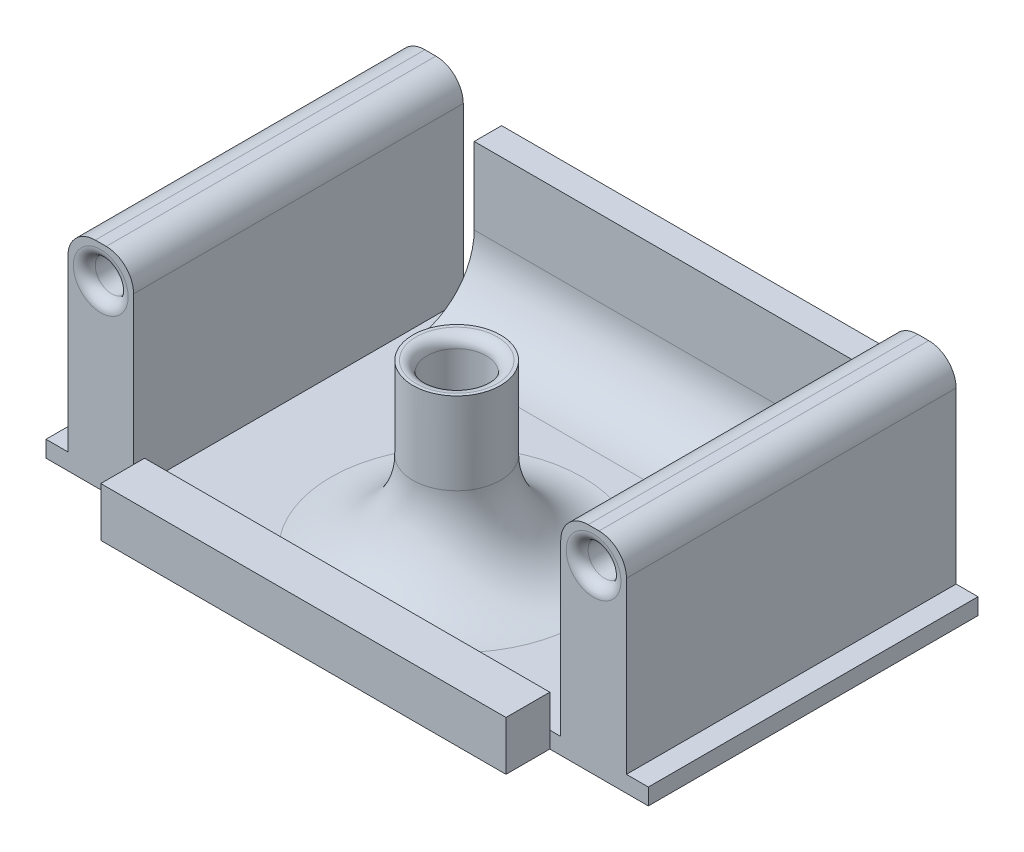
SolidWorks part; units mm, degrees
note: The reader was unsure of these and kept them because the rebuilt part matched: shared geometry of "Эскиз8<3>".
ref_plane "Спереди" through (0, 0, 0) normal (0, 0, 1) x (1, 0, 0)
ref_plane "Сверху" through (0, 0, 0) normal (0, 1, 0) x (1, 0, 0)
ref_plane "Справа" through (0, 0, 0) normal (1, 0, 0) x (0, 0, -1)
sketch "Эскиз1" plane through (0, 0, 0) normal (0, 1, 0) x (1, 0, 0)
  line L1 (-55, -30.1) -> (55, -30.1)
  line L2 (-55, -30.1) -> (-55, 30.1)
  line L3 (-55, 30.1) -> (55, 30.1)
  line L4 (55, -30.1) -> (55, 30.1)
  line L5 (0, 30.1) -> (0, -30.1) construction
  line L6 (-55, 0) -> (55, 0) construction
  point P0 (0, 0)
  dimension "D1" = 60.2
  dimension "D2" = 110
extrude "Бобышка-Вытянуть1" add sketch "Эскиз1" along normal blind 4
sketch "Эскиз2" plane through (0, 4, 0) normal (0, 1, 0) x (1, 0, 0)
  line L0 (55, 30.1) -> (-55, 30.1) construction
  line L1 (-51, -30.1) -> (-39, -30.1)
  line L2 (-51, -30.1) -> (-51, 30.1)
  line L3 (-51, 30.1) -> (-39, 30.1)
  line L4 (-39, -30.1) -> (-39, 30.1)
  line L5 (-45, 30.1) -> (-45, -30.1) construction
  line L6 (-51, 0) -> (-39, 0) construction
  line L7 (0, 38.3989) -> (0, -39.6744) construction
  line L8 (51, 30.1) -> (39, 30.1)
  line L9 (39, -30.1) -> (39, 30.1)
  line L10 (51, -30.1) -> (39, -30.1)
  line L11 (51, -30.1) -> (51, 30.1)
  point P0 (-45, 0)
  dimension "D1" = 45
  dimension "D2" = 12
extrude "Бобышка-Вытянуть2" add sketch "Эскиз2" along normal blind 36
sketch "Эскиз4" plane through (0, 0, 30.1) normal (0, 0, 1) x (1, 0, 0)
  line L0 (-45, 40) -> (-45, -5.1881) construction
  line L1 (-51, 40) -> (-39, 40) construction
  line L2 (0, 51.4646) -> (0, -25.677) construction
  line L3 (-55, 0) -> (55, 0) construction
  circle A0 centre (-45, 34) radius 3
  circle A1 centre (45, 34) radius 3
  dimension "D1" = 6
  dimension "D2" = 34
extrude "Вырез-Вытянуть1" cut sketch "Эскиз4" against normal through all
fillet "Скругление1" radius 5 4 edges at (51, 40, 0) (39, 40, 0) (-39, 40, 0) (-51, 40, 0)
sketch "Эскиз5" plane through (0, 4, 0) normal (0, 1, 0) x (1, 0, 0)
  line L0 (0, 45.2463) -> (0, -39.6744) construction
  line L2 (-39, -30.1) -> (39, -30.1) construction
  circle A0 centre (0, -10.1) radius 8
  dimension "D1" = 20
  dimension "D2" = 16
extrude "Бобышка-Вытянуть3" add sketch "Эскиз5" along normal blind 30
sketch "Эскиз6" plane through (0, 34, 0) normal (0, 1, 0) x (1, 0, 0)
  circle A0 centre (0, -10.1) radius 5.4
  dimension "D1" = 10.8
extrude "Вырез-Вытянуть2" cut sketch "Эскиз6" against normal through all
chamfer "Фаска1" [suppressed] distance 1 angle 45
fillet "Скругление3" radius 2 1 edges at (0, 34, 15.5)
sketch "Эскиз8" plane through (0, 0, 0) normal (0, 1, 0) x (1, 0, 0)
  line L0 (39, 30.1) -> (-39, 30.1) construction
  line L1 (-37, 30.1) -> (37, 30.1)
  line L2 (-37, 30.1) -> (-37, 35.1)
  line L3 (-37, 35.1) -> (37, 35.1)
  line L4 (37, 30.1) -> (37, 35.1)
  line L5 (0, 49.3413) -> (0, -35.1766) construction
  line L6 (-69.2456, 0) -> (102.8783, 0) construction
  line L7 (-37, -38.1) -> (37, -38.1)
  line L8 (37, -30.1) -> (37, -38.1)
  line L9 (-37, -30.1) -> (37, -30.1)
  line L10 (-37, -30.1) -> (-37, -38.1)
  point P9 (0, 30.1)
  point P16 (0, 0)
  line M14 (55, -30.1) -> (-55, -30.1)
  line M16 (-55, 30.1) -> (55, 30.1)
  dimension "D1" = 5
  dimension "D2" = 74
  dimension "D3" = 8
extrude "Бобышка-Вытянуть4" add sketch "Эскиз8" along normal blind 30 contours L4 L2 L3 M16
extrude "Бобышка-Вытянуть5" add sketch "Эскиз8<3>" along normal blind 10 contours L10 L8 L7 M14
sketch "Эскиз8<3>" plane through (0, 0, 0) normal (0, 1, 0) x (1, 0, 0) same geometry as "Эскиз8"
chamfer "Фаска2" distance 1 angle 45 13 edges at (46, 0, 30.1) (-37, 0, 34.1) (0, 0, 38.1) (37, 0, 34.1) (-46, 0, 30.1) (-55, 0, 0) (46, 0, -30.1) (55, 0, 0) (0, 0, 15.5) (-46, 0, -30.1) (37, 0, -32.6) (-37, 0, -32.6) (0, 0, -35.1)
fillet "Скругление5" radius 2 4 edges at (-42, 34, -30.1) (-42, 34, 30.1) (42, 34, -30.1) (42, 34, 30.1)
fillet "Скругление6" radius 12 1 edges at (0, 4, -30.1)
fillet "Скругление2" radius 15 1 edges at (0, 4, 2.1)
